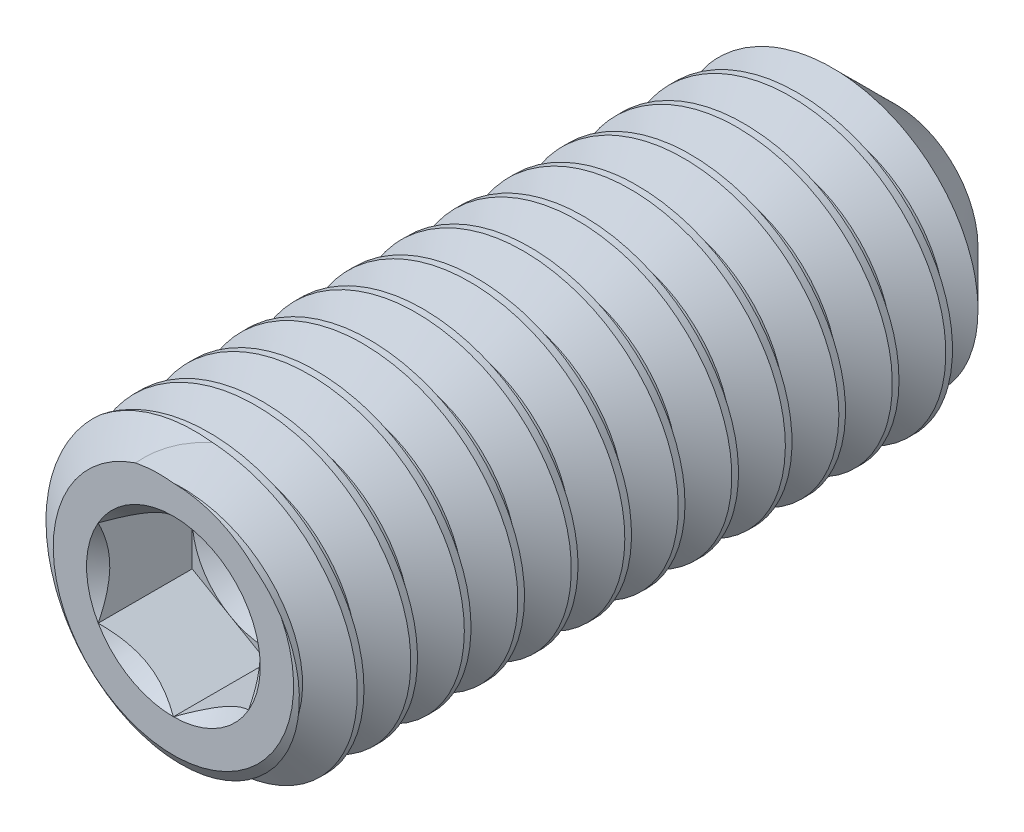
SolidWorks part; units mm, degrees
ref_plane "Front" through (0, 0, 0) normal (0, 0, 1) x (1, 0, 0)
ref_plane "Top" through (0, 0, 0) normal (0, 1, 0) x (1, 0, 0)
ref_plane "Right" through (0, 0, 0) normal (1, 0, 0) x (0, 0, -1)
sketch "Sketch22" plane through (0, 0, 0) normal (1, 0, 0) x (0, 0, -1)
  line L0 (-8.8727, 0) -> (-8.8727, 3.1699)
  line L1 (-8.8727, 3.1699) -> (-8.3178, 3.9624)
  line L2 (-8.3178, 3.9624) -> (8.3862, 3.9624)
  line L3 (8.3862, 3.9624) -> (10.1773, 2.1713)
  line L4 (10.1773, 2.1713) -> (8.8727, 0)
  line L5 (8.8727, 0) -> (-8.8727, 0)
  line L6 (8.8727, 0) -> (10.1773, 0) construction
  line L7 (10.1773, 0) -> (10.1773, 2.1713) construction
  line L8 (10.1773, -2.1713) -> (8.8727, 0) construction
  line L9 (-8.3178, -3.9624) -> (8.3862, -3.9624) construction
  line L10 (10.1773, -3.9624) -> (10.1773, 3.9624) construction
  line L11 (10.1773, 3.9624) -> (8.7662, 3.9624) construction
  point P11 (6.6495, -3.9624)
  point P15 (10.1773, 0)
  dimension "D3" = 35
  dimension "D5" = 118
  dimension "D6" = 45
  dimension "D7" = 6.3398
  dimension "D1" = 3.5278
revolve "Revolve1" add sketch "Sketch22" angle 360 about L6
ref_plane "Plane1" through (0, 0, -10.1773) normal (0, 0, 1) x (1, 0, 0)
sketch "Sketch27" plane through (0, 0, -10.1773) normal (0, 0, 1) x (1, 0, 0)
  circle A0 centre (0, 0) radius 3.9624 construction
  circle A1 centre (0, 0) radius 3.9624
sketch "Sketch23" plane through (0, 0, 8.8727) normal (0, 0, 1) x (1, 0, 0)
  line L1 (0, 2.2914) -> (-1.9844, 1.1457)
  line L2 (-1.9844, 1.1457) -> (-1.9844, -1.1457)
  line L3 (-1.9844, -1.1457) -> (0, -2.2914)
  line L4 (0, -2.2914) -> (1.9844, -1.1457)
  line L5 (1.9844, -1.1457) -> (1.9844, 1.1457)
  line L6 (1.9844, 1.1457) -> (0, 2.2914)
  circle A0 centre (0, 0) radius 1.9844 construction
extrude "Cut-Extrude10" cut sketch "Sketch23" against normal blind 2.4805
sketch "Sketch24" plane through (0, 0, 8.8727) normal (0, 0, 1) x (1, 0, 0)
  circle A0 centre (0, 0) radius 2.2914
extrude "Cut-Extrude11" cut sketch "Sketch24" against normal through all draft 45
sketch "Sketch26" plane through (0, 0, 6.3922) normal (0, 0, 1) x (1, 0, 0)
  circle A0 centre (0, 0) radius 1.9844 construction
  circle A1 centre (0, 0) radius 1.9844
extrude "Cut-Extrude12" cut sketch "Sketch26" against normal through all draft 60
sketch "Sketch31" plane through (0, 0, 0) normal (1, 0, 0) x (0, 0, -1)
  line L2 (8.8727, 0) -> (10.1773, -2.1713)
  line L3 (10.1773, 2.1713) -> (8.8727, 0)
ref_axis "Center Axis1" through (0, 0, -42.9554) along (0, 0, 1)
ref_plane "Contact Plane1" through (0, 0, -10.1773) normal (0, 0, 1) x (1, 0, 0)
ref_plane "Contact Plane2" through (0, 0, 8.8727) normal (0, 0, 1) x (1, 0, 0)
curve "Helix/Spiral1" pitch 1.4111 height 20.4611 radius 3.9624 centre (0, 0, -10.1773) axis (0, 0, 1) start towards (0, 1, 0)
sketch "Sketch32" plane through (0, 0, 0) normal (1, 0, 0) x (0, 0, -1)
  line L0 (10.0891, 4.1152) -> (11.5002, 4.1152) construction
  line L1 (11.5002, 4.1152) -> (10.7947, 2.8931) construction
  line L2 (10.7947, 2.8931) -> (10.0891, 4.1152) construction
  line L3 (10.1773, 3.9624) -> (8.7662, 3.9624) construction
  line L4 (10.7947, 2.8931) -> (10.7947, 3.0459) construction
  line L5 (10.7947, 4.1152) -> (10.7947, 3.9624) construction
  line L6 (10.7065, 3.0459) -> (10.8829, 3.0459)
  line L7 (10.1773, 3.9624) -> (11.412, 3.9624) construction
  line L8 (10.1332, 4.0388) -> (11.4561, 4.0388)
  line L9 (10.1332, 4.0388) -> (10.7065, 3.0459)
  line L10 (10.8829, 3.0459) -> (11.4561, 4.0388)
  point P11 (10.7947, 3.0459)
  point P13 (10.7947, 3.9624)
  point P17 (10.7947, 4.0388)
  dimension "D1" = 0.1764
sweep "Cut-Sweep1" cut profiles "Sketch32" path "Helix/Spiral1"
equation "\"D7@Sketch22\"=\"Dia@Sketch22\"*.8"
equation "\"D3@Helix/Spiral1\"=\"Length@Sketch22\" + \"Pitch@Sketch22\"l1\""
equation "\"hex Depth@Cut-Extrude10\" = \"Hex@Sketch23\" * .625"
equation "\"D1@Sketch22\"=\"Pitch@Sketch22\"*2.5"
equation "\"D4@Helix/Spiral1\"=\"Pitch@Sketch22\""
equation "\"D1@Sketch32\"=\"Pitch@Sketch22\"*.125"
